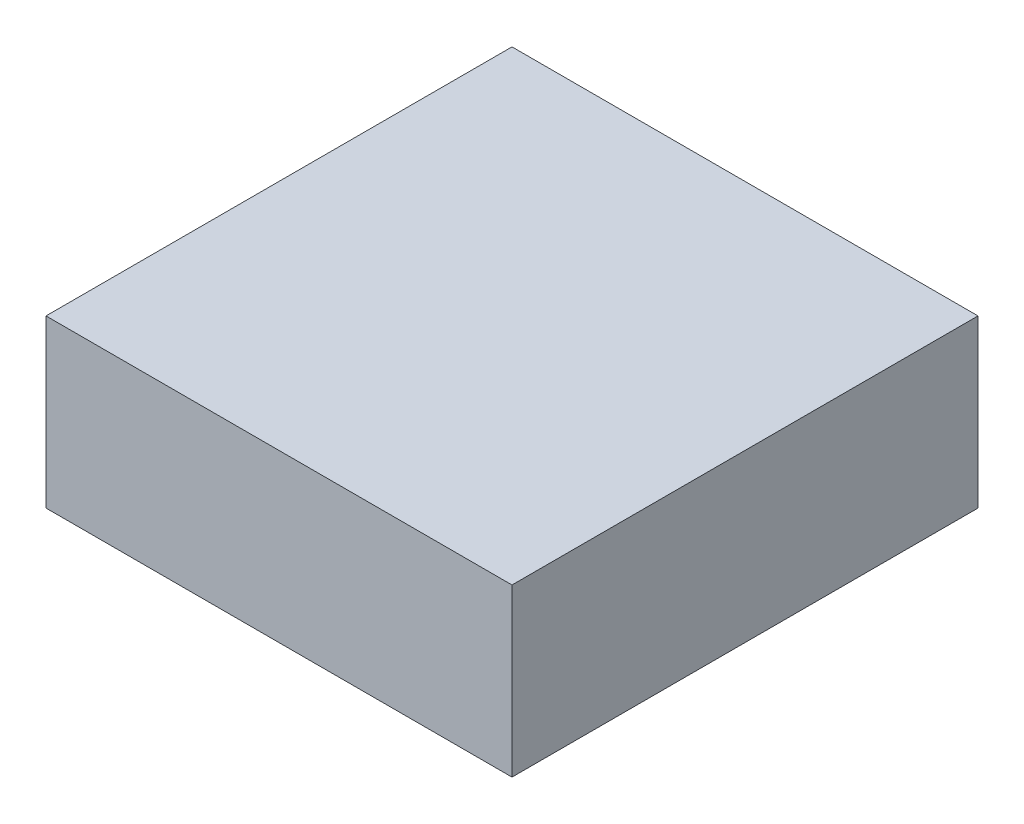
SolidWorks part; units mm, degrees
ref_plane "Alzado" through (0, 0, 0) normal (0, 0, 1) x (1, 0, 0)
ref_plane "Planta" through (0, 0, 0) normal (0, 1, 0) x (1, 0, 0)
ref_plane "Vista lateral" through (0, 0, 0) normal (1, 0, 0) x (0, 0, -1)
sketch "Croquis1" plane through (0, 0, 0) normal (0, 1, 0) x (1, 0, 0)
  line L1 (21, -21) -> (-21, -21)
  line L2 (21, -21) -> (21, 21)
  line L3 (21, 21) -> (-21, 21)
  line L4 (-21, -21) -> (-21, 21)
  line L5 (21, -21) -> (-21, 21) construction
  line L6 (21, 21) -> (-21, -21) construction
  point P0 (0, 0)
  dimension "D1" = 42
  dimension "D2" = 42
extrude "Saliente-Extruir1" add sketch "Croquis1" along normal blind 15
